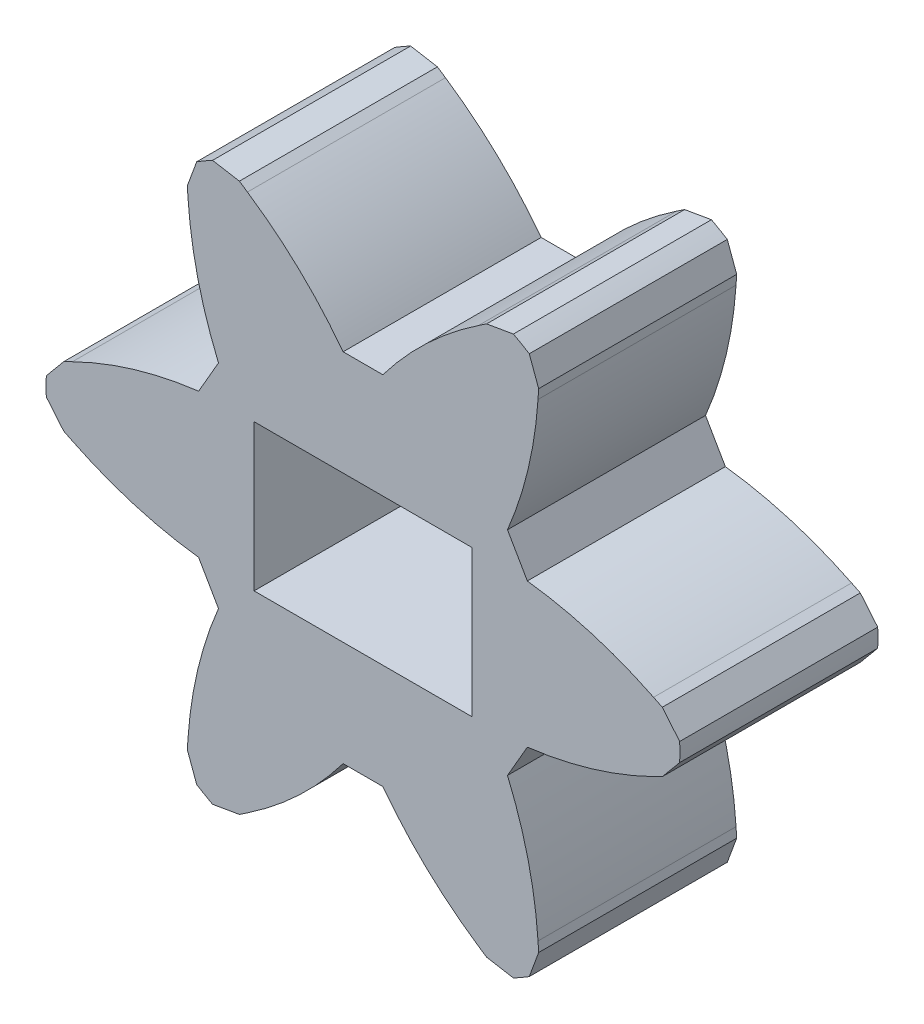
SolidWorks part; units mm, degrees
ref_plane "Front Plane" through (0, 0, 0) normal (0, 0, 1) x (1, 0, 0)
ref_plane "Top Plane" through (0, 0, 0) normal (0, 1, 0) x (1, 0, 0)
ref_plane "Right Plane" through (0, 0, 0) normal (1, 0, 0) x (0, 0, -1)
sketch "Sketch1" plane through (0, 0, 0) normal (0, 0, 1) x (1, 0, 0)
  line L0 (-2.75, 1.85) -> (2.75, 1.85)
  line L1 (1.2374, -1.2374) -> (-1.2374, -1.2374) construction
  line L2 (1.2374, -1.2374) -> (1.2374, 1.2374) construction
  line L3 (1.2374, 1.2374) -> (-1.2374, 1.2374) construction
  line L4 (-1.2374, -1.2374) -> (-1.2374, 1.2374) construction
  line L5 (1.2374, -1.2374) -> (-1.2374, 1.2374) construction
  line L6 (1.2374, 1.2374) -> (-1.2374, -1.2374) construction
  line L7 (2.75, 1.85) -> (2.75, -1.85)
  line L8 (2.75, -1.85) -> (-2.75, -1.85)
  line L9 (-2.75, -1.85) -> (-2.75, 1.85)
  circle A0 centre (0, 0) radius 8
  circle A1 centre (0, 0) radius 1.75 construction
  point P11 (0, 1.85)
  point P13 (-2.75, 0)
  dimension "D1" = 16
  dimension "D2" = 3.5
  dimension "D3" = 5.5
  dimension "D4" = 3.7
extrude "Boss-Extrude1" add sketch "Sketch1" along normal blind 5
sketch "Sketch2" plane through (0, 0, 0) normal (0, 0, 1) x (1, 0, 0)
  line L0 (0, 0) -> (0, 10.088) construction
  line L8 (-7.3319, 22.2218) -> (0, 24.9522)
  line L11 (-1.3301, 5.7236) -> (-3.121, 6.924)
  line L12 (-3.121, 6.924) -> (-3.7984, 7.0407)
  line L13 (-3.7984, 7.0407) -> (-7.3319, 22.2218)
  line L19 (-1.3301, 5.7236) -> (-0.5015, 4.5026)
  line L20 (-0.5015, 4.5026) -> (0.5015, 4.5026)
  line L21 (1.3301, 5.7236) -> (0.5015, 4.5026)
  line L22 (3.7984, 7.0407) -> (7.3319, 22.2218)
  line L23 (3.121, 6.924) -> (3.7984, 7.0407)
  line L24 (1.3301, 5.7236) -> (3.121, 6.924)
  line L25 (7.3319, 22.2218) -> (0, 24.9522)
  circle A14 centre (0, 0) radius 8 construction
  point P9 (0, 4.5026)
  point P16 (0, 8)
extrude "Cut-Extrude1" cut sketch "Sketch2" along normal through all
pattern_circular "CirPattern1" count 6 over 360 about axis through (0, 0, 5) along (0, 0, -1) of "Cut-Extrude1" reverse direction yes
sketch "Sketch3" plane through (0, 0, 0) normal (0, 0, 1) x (1, 0, 0)
  circle A0 centre (0, 0) radius 7.5
  dimension "D1" = 15
fillet "Fillet1" radius 10 12 edges at (-1.3301, -5.7236, 2.5) (5.6218, 1.7099, 2.5) (4.2918, -4.0137, 2.5) (5.6218, -1.7099, 2.5) (1.3301, -5.7236, 2.5) (-4.2918, -4.0137, 2.5) (-5.6218, -1.7099, 2.5) (-5.6218, 1.7099, 2.5) (-4.2918, 4.0137, 2.5) (4.2918, 4.0137, 2.5) (1.3301, 5.7236, 2.5) (-1.3301, 5.7236, 2.5)
